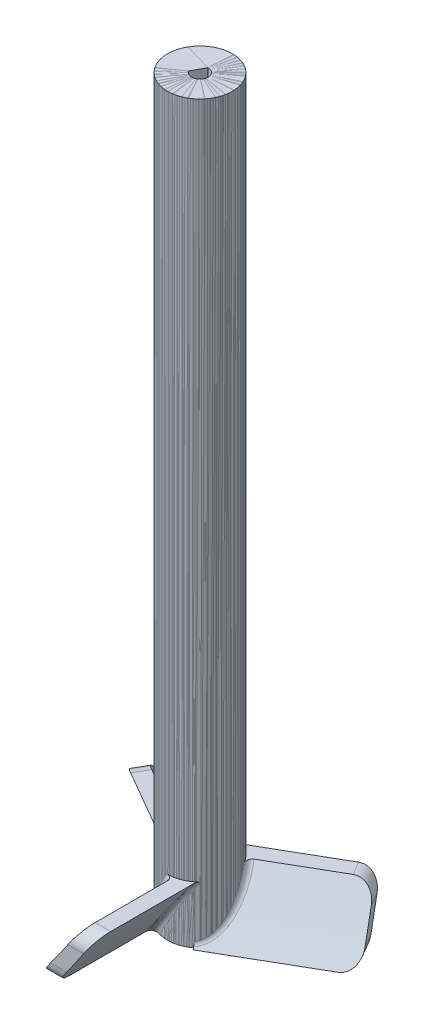
SolidWorks part; units mm, degrees
ref_plane "Front Plane" through (0, 0, 0) normal (0, 0, 1) x (1, 0, 0)
ref_plane "Top Plane" through (0, 0, 0) normal (0, 1, 0) x (1, 0, 0)
ref_plane "Right Plane" through (0, 0, 0) normal (1, 0, 0) x (0, 0, -1)
sketch "Sketch7" plane through (0, 0, 0) normal (0, 0, 1) x (1, 0, 0)
  line L0 (3.5176, 0) -> (-3.5176, 0) construction
  line L1 (6.849, 7) -> (4.9497, 7)
  line L2 (0, 0) -> (2, 0)
  arc A0 (0, 0) -> (4.9497, 7) centre (-91.3778, 69.8639) ccw
  arc A1 (6.849, 7) -> (2, 0) centre (-91.3778, 69.8639) cw
  dimension "D2" = 7
extrude "Boss-Extrude2" add sketch "Sketch7" along normal blind 15 contours A0 L1 A1 L2
fillet "Fillet1" radius 2 2 edges at (1, 0, 15) (5.8994, 7, 15)
sketch "Sketch10" plane through (0, 0, 0) normal (0, 1, 0) x (1, 0, 0)
  line L0 (0.3156, 0) -> (8.1957, 0) construction
  line L1 (4.9497, 0) -> (0, 0) construction
  line L2 (6.849, 0) -> (4.9497, 0) construction
  line L3 (2, 0) -> (6.849, 0) construction
  line L4 (4.2556, 0) -> (4.2556, 0.5251)
  line L5 (3.1481, -1000) -> (3.1481, 49000) construction
  circle A0 centre (4.2556, 0.5251) radius 3.9749
  point P5 (3.1481, 0)
  point P10 (-1.8519, 0)
  point P14 (0, 0)
  point P16 (0, 0)
  point P17 (3.1481, 0)
  point P18 (0, 0)
  point P19 (0, 0)
  point P20 (0, 0)
  dimension "D4" = 5
extrude "Boss-Extrude3" add sketch "Sketch10" along normal blind 90 contours A0 region at (0.3932, 0, -0.5251)
fillet "Fillet4" radius 0.7 2 edges at (1.5922, 2.1332, 2.4254) (3.7358, 2.3821, 3.4156)
pattern_circular "CirPattern1" count 3 over 360 about axis through (4.2556, 90, -0.5251) along (0, -1, 0) of bodies 103 102
sketch "Sketch11" plane through (0, 90, 0) normal (0, 1, 0) x (1, 0, 0)
  line L0 (3.4046, 0) -> (4.2264, 1.5247)
  arc A1 (3.4046, 0) -> (4.2264, 1.5247) centre (4.2556, 0.5251) ccw
  circle A2 centre (4.2556, 0.5251) radius 3.9749 construction
extrude "Cut-Extrude1" cut sketch "Sketch11" against normal blind 40 contours A1 L0
equation "\"insidebladediameter\"=0.01"
equation "\"height\"= 0.007"
equation "\"bladethickness\"=0.002"
equation "\"insidebladeradius\"= \"insidebladediameter\" / 2"
equation "\"D1@Sketch7\"=\"bladethickness\""
equation "\"D2@Sketch7\"=\"height\""
equation "\"bladewidth\"= \"height\" * cos ( \"bladeangle\" )"
equation "\"bladelength\"= 0.015"
equation "\"D1@Boss-Extrude2\"=\"bladelength\""
equation "\"bladetipradius\"= 0.002"
equation "\"D1@Fillet1\"=\"bladetipradius\""
equation "\"fusedistance\"= 0.0045"
equation "\"motorrodheight\"=0.09"
equation "\"D1@Boss-Extrude3\"=\"motorrodheight\""
equation "\"numberofblades\"= 3"
equation "\"D1@CirPattern1\"=\"numberofblades\""
equation "\"roddiameter\"= ( \"bladewidth\" + 0.003 )"
equation "\"roddepth\"= 0.005"
equation "\"bladeangle\"= 45deg"
equation "\"m\"=1"
equation "\"flatfacedist\"= 0.0005"
equation "\"motorshaftdiameter\"=0.002"
equation "\"D1@Sketch11\"=\"motorshaftdiameter\"/2"
equation "\"D3@Sketch7\"=\"bladewidth\""
equation "\"D2@Sketch10\"=\"roddiameter\"/2-\"fusedistance\""
equation "\"D1@Sketch10\"=\"roddiameter\""
equation "\"D2@Sketch11\"=\"flatfacedist\""
equation "\"bladefilletradius\"= 0.0007"
equation "\"D1@Fillet4\"=\"bladefilletradius\""
